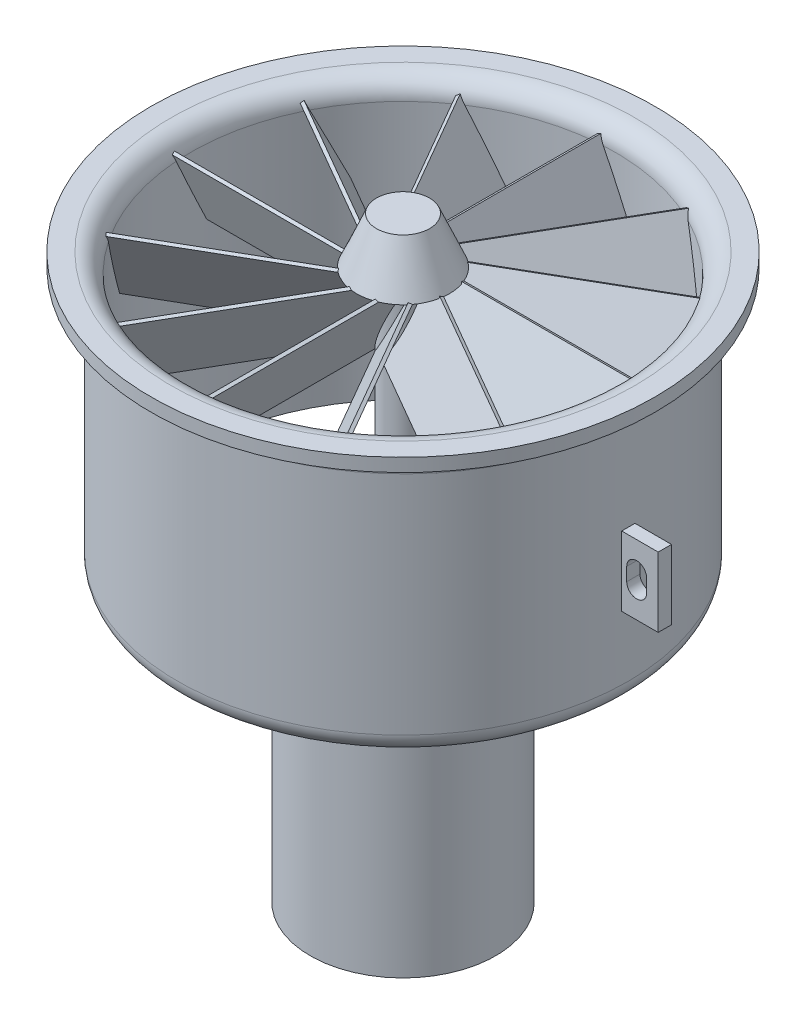
SolidWorks part; units mm, degrees
material "PA Type 6"
ref_plane "Front Plane" through (0, 0, 0) normal (0, 0, 1) x (1, 0, 0)
ref_plane "Top Plane" through (0, 0, 0) normal (0, 1, 0) x (1, 0, 0)
ref_plane "Right Plane" through (0, 0, 0) normal (1, 0, 0) x (0, 0, -1)
sketch "Sketch2" plane through (0, 0, 0) normal (0, 0, 1) x (1, 0, 0)
  line L1 (32, 5.3502) -> (32, 45)
  line L2 (32, 45) -> (38, 45)
  line L3 (38, 45) -> (38, 43)
  line L4 (38, 43) -> (34, 43)
  line L5 (34, 43) -> (34, 3.3502)
  line L8 (3, 5.3502) -> (3, 43)
  line L9 (3, 43) -> (7, 43)
  line L10 (7, 43) -> (4, 50)
  line L11 (4, 50) -> (0, 50)
  line L12 (0, 50) -> (0, 0)
  line L13 (3, 5.3502) -> (32, 5.3502)
  line L14 (34, 3.3502) -> (15, 0)
  line L15 (15, 0) -> (0, 0) construction
  line L18 (14, -40) -> (8, -43.4641)
  line L19 (8, -43.4641) -> (3, -43.4641)
  line L20 (0, -45) -> (0, 0)
  line L21 (3, -43.4641) -> (3, -45)
  line L22 (3, -45) -> (0, -45)
  line L23 (14, 0) -> (14, -40)
  line L24 (14, 0) -> (15, 0)
  dimension "D5" = 2
  dimension "D8" = 3
  dimension "D9" = 4
  dimension "D10" = 4
  dimension "D2" = 45
  dimension "D3" = 32
  dimension "D4" = 34
  dimension "D6" = 50
  dimension "D7" = 15
  dimension "D11" = 170
  dimension "D12" = 2
  dimension "D13" = 38
  dimension "D14" = 95
  dimension "D16" = 3
  dimension "D18" = 5
  dimension "D17" = 14
  dimension "D15" = 40
  dimension "D19" = 120
revolve "Revolve1" add sketch "Sketch2" angle 360 about L12
sketch "Sketch3" plane through (0, 0, 0) normal (0, -1, 0) x (1, 0, 0)
  line L0 (0, 0) -> (0, 34) construction
  line L1 (0, 0) -> (-24.0416, 24.0416) construction
  line L2 (-24.0416, 24.0416) -> (-9.8995, 9.8995) construction
  line L3 (0, 34) -> (0, 14) construction
  line L4 (-21.169, 23.9974) -> (-9.8108, 12.6392)
  line L5 (-2, 31.9374) -> (-2, 15.8745)
  circle A0 centre (0, 0) radius 34 construction
  arc A1 (0, 34) -> (-24.0416, 24.0416) centre (0, 0) ccw construction
  arc A4 (-2, 31.9374) -> (-21.169, 23.9974) centre (0, 0) ccw
  arc A5 (-2, 15.8745) -> (-9.8108, 12.6392) centre (0, 0) ccw
  arc A7 (0, 14) -> (-9.8995, 9.8995) centre (0, 0) ccw construction
  arc A8 (-9.8995, 9.8995) -> (0, 14) centre (0, 0) cw construction
  circle A9 centre (0, 0) radius 14 construction
  dimension "D1" = 45
extrude "Cut-Extrude1" cut sketch "Sketch3" against normal through all
pattern_circular "CirPattern1" count 8 over 360 about axis through (0, 50, 0) along (0, 1, 0) of "Cut-Extrude1" reverse direction yes
sketch "Sketch5" plane through (0, 0, 0) normal (0, 0, 1) x (1, 0, 0)
  line L0 (0, 0) -> (0, 50) construction
  line L1 (4, 50) -> (-4, 50) construction
  line L2 (-2.5357, 32.23) -> (2.5357, 43.1057) construction
  line L3 (-2.3091, 32.1243) -> (2.7623, 43)
  line L4 (-2.7623, 32.3356) -> (2.3091, 43.2113)
  line L5 (2.3091, 43.2113) -> (2.7623, 43)
  line L7 (-7, 43) -> (7, 43) construction
  line L8 (-2.5357, 32.23) -> (2.5357, 43.1057) construction
  line L9 (-2.3091, 32.1243) -> (2.7623, 43) construction
  line L10 (-2.7623, 32.3356) -> (-2.3091, 32.1243)
  point P10 (0, 37.6678)
  dimension "D2" = 25
  dimension "D3" = 12
  dimension "D1" = 0.25
extrude "Boss-Extrude1" add sketch "Sketch5" along normal up to surface (31.9166 mm away) up to face at (-32, 45, 0)
pattern_circular "CirPattern2" count 12 over 360 about axis through (0, 50, 0) along (0, 1, 0) of "Boss-Extrude1" reverse direction yes
fillet "Fillet1" radius 3 3 edges at (-32, 45, 0) (-34, 43, 0) (-34, 3.3502, 0)
sketch "Sketch6" plane through (0, 0, 0) normal (0, 0, 1) x (1, 0, 0)
  line L0 (0, 0) -> (0, 50) construction
  line L1 (-39.5, 26) -> (-33, 26)
  line L2 (-39.5, 26) -> (-39.5, 15.5)
  line L3 (-39.5, 15.5) -> (-33, 15.5)
  line L4 (-33, 26) -> (-33, 15.5)
  line L5 (4, 50) -> (-4, 50) construction
  line L6 (39.5, 15.5) -> (33, 15.5)
  line L7 (33, 26) -> (33, 15.5)
  line L8 (39.5, 26) -> (33, 26)
  line L9 (39.5, 26) -> (39.5, 15.5)
  line L11 (-39.5, 20.75) -> (-33, 20.75) construction
  line L12 (-36.25, 19.75) -> (-36.25, 21.75) construction
  line L13 (-37.75, 19.75) -> (-37.75, 21.75)
  line L14 (-34.75, 19.75) -> (-34.75, 21.75)
  line L15 (36.25, 19.75) -> (36.25, 21.75) construction
  line L16 (37.75, 19.75) -> (37.75, 21.75)
  line L17 (34.75, 19.75) -> (34.75, 21.75)
  arc A0 (-37.75, 19.75) -> (-34.75, 19.75) centre (-36.25, 19.75) ccw
  arc A1 (-34.75, 21.75) -> (-37.75, 21.75) centre (-36.25, 21.75) ccw
  arc A2 (37.75, 19.75) -> (34.75, 19.75) centre (36.25, 19.75) cw
  arc A3 (34.75, 21.75) -> (37.75, 21.75) centre (36.25, 21.75) cw
  point P19 (-36.25, 20.75)
  point P26 (36.25, 20.75)
  dimension "D1" = 66
  dimension "D2" = 79
  dimension "D3" = 10.5
  dimension "D5" = 3
  dimension "D6" = 2
  dimension "D4" = 34.5
extrude "Boss-Extrude2" add sketch "Sketch6" against normal mid plane 2
equation "\"EDF_ID\"= 64"
equation "\"EDF_Lip_Dia\"= 76"
equation "\"EDF_OD\"= 68"
equation "\"EDF_Duct_Height\"= 45"
equation "\"EDF_Duct_Thickness\"= 2"
equation "\"D5@Sketch2\"=\"EDF_Duct_Thickness\""
equation "\"EDF_Thrust_Cone_Height\"= 50"
equation "\"D2@Sketch2\"=\"EDF_Duct_Height\""
equation "\"D3@Sketch2\"=\"EDF_ID\"/2"
equation "\"D4@Sketch2\"=\"EDF_OD\"/2"
equation "\"D6@Sketch2\"=\"EDF_Thrust_Cone_Height\""
equation "\"EDF_Motor_Diameter\"= 28"
equation "\"D7@Sketch2\"=\"EDF_Motor_Diameter\" / 2 + 1"
equation "\"D12@Sketch2\"=\"EDF_Duct_Thickness\""
equation "\"D13@Sketch2\"=\"EDF_Lip_Dia\" / 2"
equation "\"D1@Sketch3\"=360/8"
equation "\"D2@Sketch3\"=\"EDF_Duct_Thickness\""
equation "\"EDF_Assembly_Height\"= 95"
equation "\"D14@Sketch2\"=\"EDF_Assembly_Height\""
equation "\"Motor_Stator_Height\"= 40"
equation "\"Motor_Shaft_Diameter\"= 6"
equation "\"D16@Sketch2\"=\"Motor_Shaft_Diameter\" / 2"
equation "\"D17@Sketch2\"=\"EDF_Motor_Diameter\" / 2"
equation "\"D15@Sketch2\"=\"Motor_Stator_Height\""
equation "\"D1@Sketch6\"=\"EDF_ID\" + 2mm"
equation "\"Mounting_Tab_OD\"= 79"
equation "\"D2@Sketch6\"=\"Mounting_Tab_OD\""
equation "\"Mounting_Tab_Height\"= 10.5"
equation "\"D3@Sketch6\"=\"Mounting_Tab_Height\""
equation "\"Mounting_Tab_Position\"= 34.5"
equation "\"Mounting_Tab_Slot_Diam\"= 3"
equation "\"D5@Sketch6\"=\"Mounting_Tab_Slot_Diam\""
equation "\"Mounting_Tab_Slot_CC\"= 2"
equation "\"D6@Sketch6\"=\"Mounting_Tab_Slot_CC\""
equation "\"Mounting_Tab_Thickness\"= 2"
equation "\"D1@Boss-Extrude2\"=\"Mounting_Tab_Thickness\""
equation "\"D4@Sketch6\"=\"Mounting_Tab_Position\""
